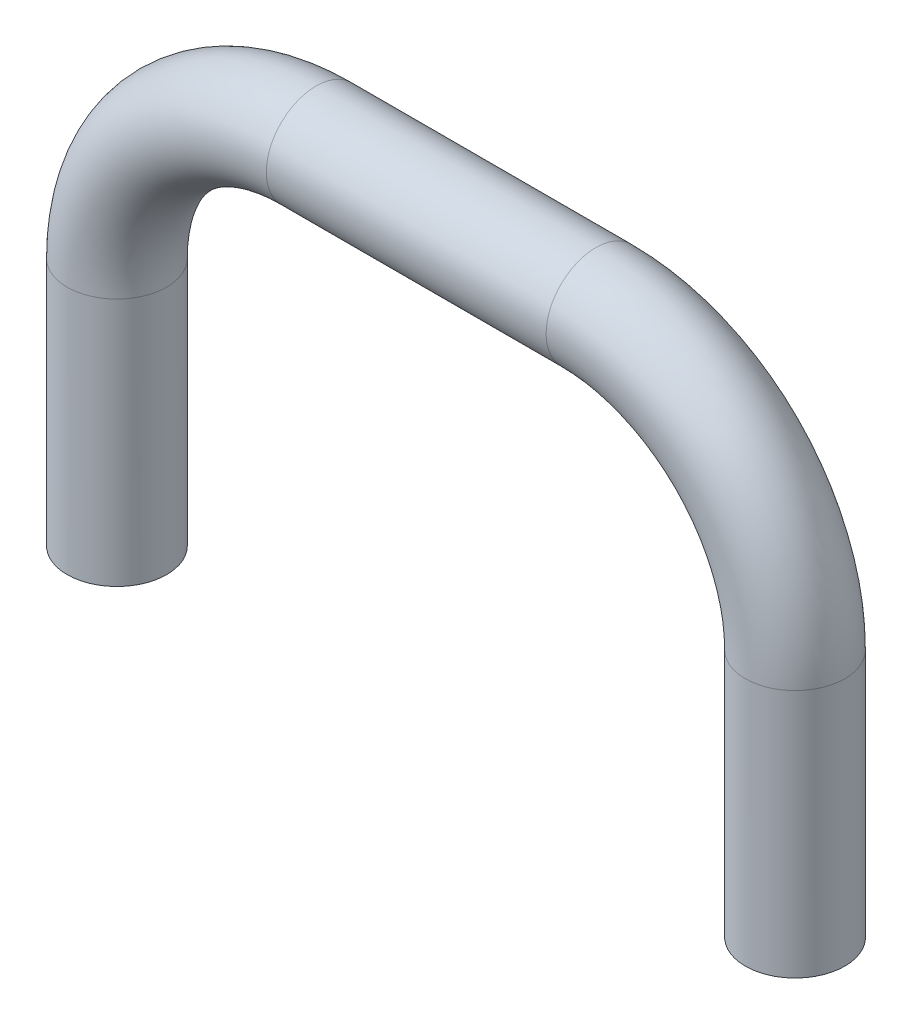
SolidWorks part; units mm, degrees
material "Простая углеродистая сталь"
ref_plane "Front" through (0, 0, 0) normal (0, 0, 1) x (1, 0, 0)
ref_plane "Top" through (0, 0, 0) normal (0, 1, 0) x (1, 0, 0)
ref_plane "Right" through (0, 0, 0) normal (1, 0, 0) x (0, 0, -1)
sketch "Эскиз1" plane through (0, 0, 0) normal (0, 0, 1) x (1, 0, 0)
  line L0 (0, 0) -> (0, 25)
  line L1 (20, 45) -> (48.1, 45)
  line L2 (68.1, 25) -> (68.1, 0)
  line L3 (0, 0) -> (88.1644, 0) construction
  arc A0 (48.1, 45) -> (68.1, 25) centre (48.1, 25) cw
  arc A1 (0, 25) -> (20, 45) centre (20, 25) cw
  point P6 (68.1, 45)
  point P12 (0, 45)
  dimension "D2" = 20
  dimension "D1" = 68.1
  dimension "D4" = 45
ref_plane "Плоскость1" through (0, 0, 0) normal (0, 1, 0) x (1, 0, 0)
sketch "Эскиз2" plane through (0, 0, 0) normal (0, 1, 0) x (1, 0, 0)
  circle A0 centre (0, 0) radius 5
  dimension "D1" = 10
sweep "По траектории1" add profiles "Эскиз2" path "Эскиз1"
hole_wizard "Сверло под метчик  спиральное M51" positions "Эскиз4" profile "Эскиз3" hole size "M5x0.8" standard "DIN"
sketch "Эскиз4" plane through (0, 0, 0) normal (0, -1, 0) x (-1, 0, 0)
  point P0 (0, 0)
  point P3 (-68.1, 0)
sketch "Эскиз3" plane through (0, 0, 0) normal (1, 0, 0) x (0, 0, -1)
  line L0 (0, 0) -> (0, 11.5622)
  line L1 (0, 11.5622) -> (2.6, 10)
  line L2 (2.6, 10) -> (2.6, 0)
  line L5 (2.6, 0) -> (0, 0)
  line L10 (0, 11.5622) -> (-2.6, 10) construction
  line L11 (0, -6.35) -> (0, 107.95) construction
  dimension "Диаметр отверстия" = 5.2
  dimension "Глубина отверстия" = 10
  dimension "Угол заточки сверла" = 118
